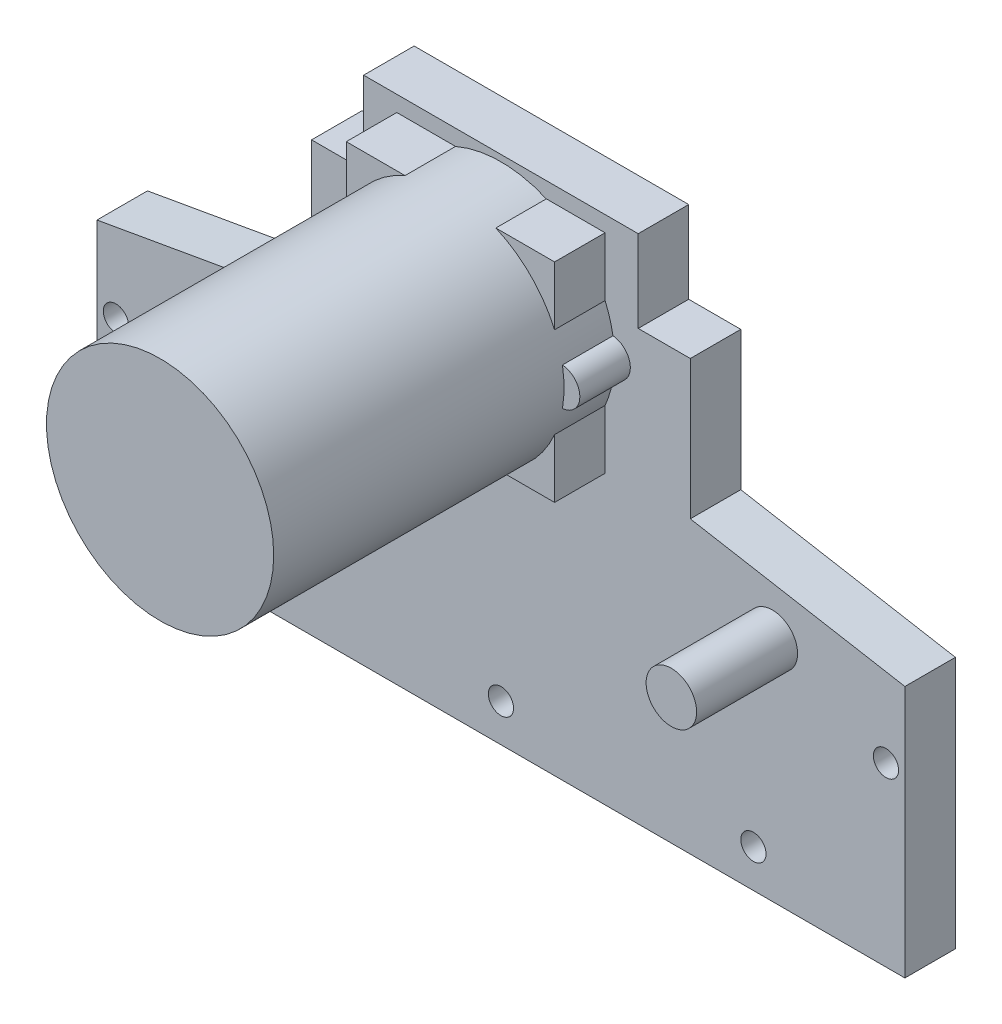
SolidWorks part; units mm, degrees
material "Nickel"
ref_plane "Front Plane" through (0, 0, 0) normal (0, 0, 1) x (1, 0, 0)
ref_plane "Top Plane" through (0, 0, 0) normal (0, 1, 0) x (1, 0, 0)
ref_plane "Right Plane" through (0, 0, 0) normal (1, 0, 0) x (0, 0, -1)
sketch "Sketch1" plane through (0, 0, 0) normal (0, 0, 1) x (1, 0, 0)
  line L0 (-32, 0) -> (32, 0)
  line L1 (-1015.4659, 23) -> (48984.5341, 23) construction
  line L2 (-15, 23) -> (15, 23)
  line L3 (-32, 0) -> (-32, 20)
  line L4 (-32, 20) -> (-15, 23)
  line L5 (32, 0) -> (32, 20)
  line L6 (32, 20) -> (15, 23)
  line L7 (-15, 23) -> (-15, 34)
  line L8 (-15, 34) -> (15, 34)
  line L9 (15, 34) -> (15, 23)
  line L10 (-1006.9308, 40.5) -> (48993.0692, 40.5) construction
  line L11 (-10.875, 40.5) -> (10.875, 40.5)
  line L12 (-10.875, 40.5) -> (-10.875, 34)
  line L13 (10.875, 40.5) -> (10.875, 34)
  line L14 (0, 34) -> (0, 40.5) construction
  dimension "D1" = 64
  dimension "D2" = 23
  dimension "D3" = 30
  dimension "D4" = 20
  dimension "D5" = 11
  dimension "D6" = 6.5
  dimension "D7" = 21.75
extrude "Boss-Extrude1" add sketch "Sketch1" along normal blind 4 contours L5 L6 L2 L4 L3 L0 | L9 L8 L7 L2 | L13 L11 L12 L8 region at (0, 11.1232, 0) region at (0, 28.5, 0) region at (0, 37.25, 0)
sketch "Sketch2" plane through (0, 0, 4) normal (0, 0, 1) x (1, 0, 0)
  line L0 (-1024.4669, 3) -> (48975.5331, 3) construction
  line L1 (-32, 0) -> (32, 0) construction
  line L2 (-20, 3) -> (20, 3)
  line L3 (-32, 0) -> (-32, 20) construction
  line L4 (0, -997) -> (0, 49003) construction
  circle A0 centre (-20, 3) radius 1
  circle A1 centre (20, 3) radius 1
  circle A2 centre (0, 3) radius 1
  circle A3 centre (-30.5, 14) radius 1
  circle A4 centre (30.5, 14) radius 1
  dimension "D3" = 2
  dimension "D1" = 40
  dimension "D2" = 3
  dimension "D5" = 14
  dimension "D6" = 1.5
extrude "Cut-Extrude1" cut sketch "Sketch2" against normal blind 5 contours A3 | A1 | A0 | A2 | A4 region at (20, 3.9717, 4) region at (-30.5, 14, 4)
sketch "Sketch3" plane through (0, 0, 4) normal (0, 0, 1) x (1, 0, 0)
  line L0 (0, 40.5) -> (0, 0) construction
  line L1 (-10.875, 40.5) -> (10.875, 40.5) construction
  line L2 (-32, 0) -> (32, 0) construction
  line L4 (-8.5, 39.5) -> (8.5, 39.5)
  line L5 (-8.5, 39.5) -> (-8.5, 22.5)
  line L6 (-8.5, 22.5) -> (8.5, 22.5)
  line L7 (8.5, 39.5) -> (8.5, 22.5)
  circle A0 centre (0, 31) radius 9
  circle A1 centre (0, 31) radius 8.5
  dimension "D1" = 18
  dimension "D2" = 17
  dimension "D3" = 17
  dimension "D4" = 1
extrude "Boss-Extrude2" add sketch "Sketch3" along normal blind 27 contours A0
sketch "Sketch4" plane through (0, 0, 31) normal (0, 0, 1) x (1, 0, 0)
  circle A0 centre (0, 31) radius 9
sketch "Sketch5" plane through (0, 0, 0) normal (0, 0, -1) x (-1, 0, 0)
  line L0 (32, 0) -> (-32, 0) construction
  line L1 (-5, 10) -> (13, 10)
  line L2 (-5, 10) -> (-5, 28)
  line L3 (-5, 28) -> (13, 28)
  line L4 (13, 10) -> (13, 28)
  line L5 (32, 0) -> (32, 20) construction
  line L6 (15, 23) -> (15, 34) construction
  dimension "D1" = 28
  dimension "D2" = 19
  dimension "D3" = 20
  dimension "D4" = 10
extrude "Boss-Extrude3" add sketch "Sketch5" along normal blind 3
sketch "Sketch6" plane through (0, 0, 4) normal (0, 0, 1) x (1, 0, 0)
  line L0 (21.5, 18) -> (-21.5, 18) construction
  line L1 (0, 0) -> (0, 18) construction
  line L2 (-32, 0) -> (32, 0) construction
  circle A0 centre (21.5, 18) radius 2
  circle A1 centre (-21.5, 18) radius 2
  dimension "D2" = 4
  dimension "D1" = 43
  dimension "D3" = 18
extrude "Boss-Extrude4" add sketch "Sketch6" along normal blind 8
sketch "Sketch7" plane through (0, 0, 4) normal (0, 0, 1) x (1, 0, 0)
  line L0 (-10.25, 41.25) -> (-10.25, 20.75) construction
  line L1 (-8.25, 39.25) -> (8.25, 39.25)
  line L2 (-8.25, 39.25) -> (-8.25, 22.75)
  line L3 (-8.25, 22.75) -> (8.25, 22.75)
  line L4 (8.25, 39.25) -> (8.25, 22.75)
  line L5 (-8.25, 39.25) -> (8.25, 22.75) construction
  line L6 (-8.25, 22.75) -> (8.25, 39.25) construction
  line L7 (-10.25, 20.75) -> (10.25, 20.75) construction
  line L8 (10.25, 41.25) -> (10.25, 20.75) construction
  line L9 (-10.25, 41.25) -> (10.25, 41.25) construction
  circle A0 centre (0, 31) radius 9 construction
  circle A2 centre (-8.75, 31) radius 1.5
  circle A3 centre (8.75, 31) radius 1.5
  point P0 (0, 31)
  dimension "D3" = 3
  dimension "D1" = 16.5
  dimension "D2" = 2
extrude "Boss-Extrude5" add sketch "Sketch7" along normal blind 4 contours A2 | L2 L3 L4 L1 | A3
